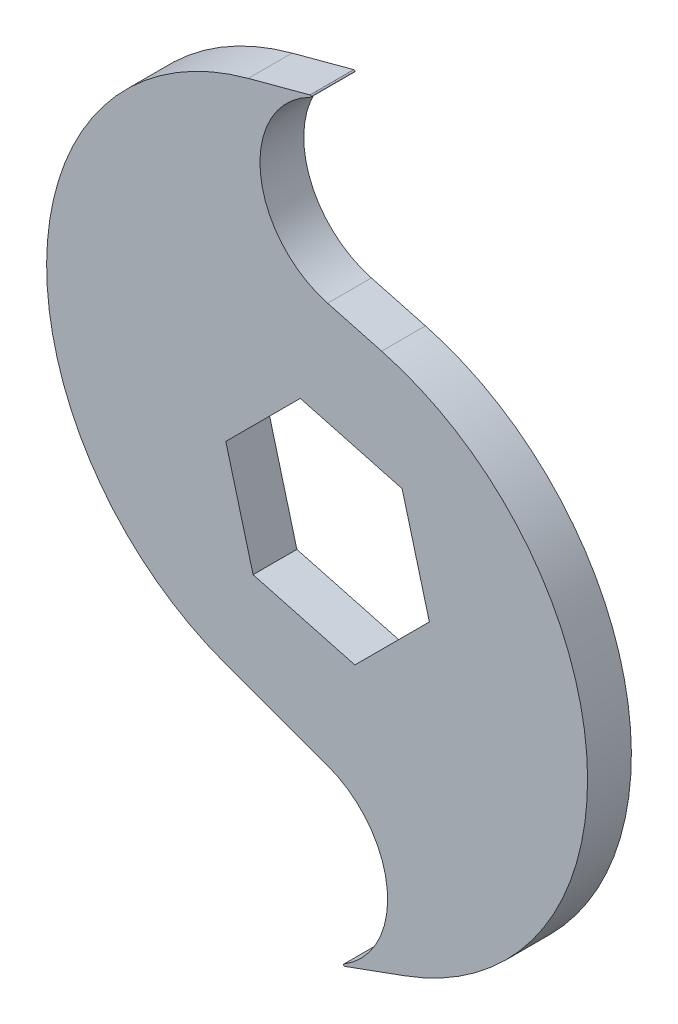
SolidWorks part; units mm, degrees
ref_plane "Front Plane" through (0, 0, 0) normal (0, 0, 1) x (1, 0, 0)
ref_plane "Top Plane" through (0, 0, 0) normal (0, 1, 0) x (1, 0, 0)
ref_plane "Right Plane" through (0, 0, 0) normal (1, 0, 0) x (0, 0, -1)
sketch "Sketch1" plane through (0, 0, 0) normal (0, 0, 1) x (1, 0, 0)
  line L0 (0, 52.07) -> (-11.0405, 49.1117)
  line L1 (0, 52.07) -> (0, 0) construction
  line L2 (0, -52.07) -> (10.7407, -48.1607)
  line L3 (0, 0) -> (0, -52.07) construction
  line L5 (-3.7955, 14.165) -> (-14.165, 3.7955)
  line L6 (-14.165, 3.7955) -> (-10.3695, -10.3695)
  line L7 (-10.3695, -10.3695) -> (3.7955, -14.165)
  line L8 (3.7955, -14.165) -> (14.165, -3.7955)
  line L9 (14.165, -3.7955) -> (10.3695, 10.3695)
  line L10 (10.3695, 10.3695) -> (-3.7955, 14.165)
  line L11 (0, 27.5355) -> (7.5237, 25.5195)
  line L12 (0, -28.2018) -> (-14.1906, -23.0368)
  circle A0 centre (0, 0) radius 52.07 construction
  arc A1 (0, 52.07) -> (0, 27.5355) centre (3.287, 39.8027) ccw
  arc A3 (0, -52.07) -> (0, -28.2018) centre (-4.3437, -40.1359) ccw
  arc A4 (10.7407, -48.1607) -> (7.5237, 25.5195) centre (-2.4834, -11.8278) ccw
  arc A5 (-11.0405, 49.1117) -> (-14.1906, -23.0368) centre (-1.2414, 12.5408) ccw
  circle A6 centre (0, 0) radius 12.7 construction
  point P12 (8.7828, 11.7437)
  dimension "D4" = 70
  dimension "D5" = 25.4
  dimension "D1" = 104.14
  dimension "D6" = 12.7
  dimension "D2" = 11.43
  dimension "D3" = 75
  dimension "D7" = 15
extrude "Boss-Extrude1" add sketch "Sketch1" along normal mid plane 6.096
fillet "Fillet1" radius 0.127 2 edges at (0, 52.07, 0) (0, -52.07, 0)
